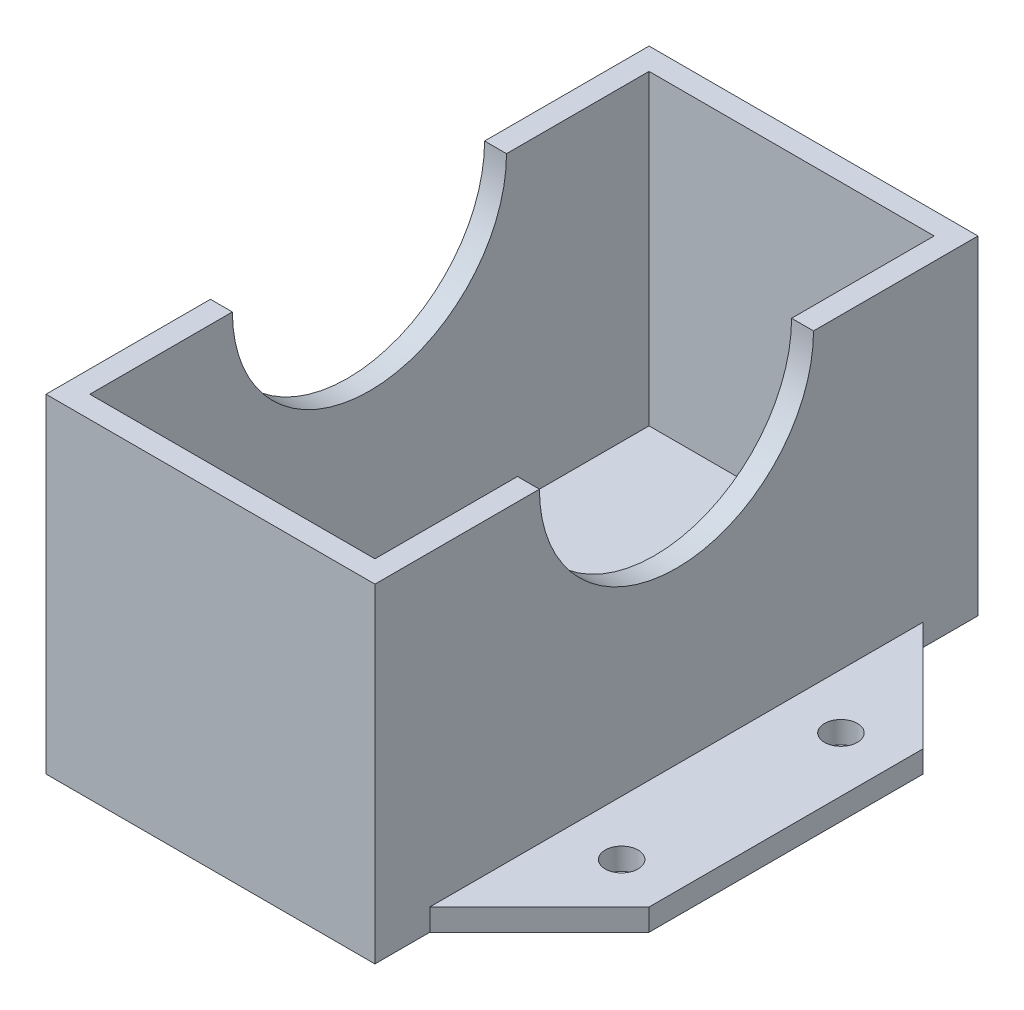
SolidWorks part; units mm, degrees
material "PLA 50%"
ref_plane "Front Plane" through (0, 0, 0) normal (0, 0, 1) x (1, 0, 0)
ref_plane "Top Plane" through (0, 0, 0) normal (0, 1, 0) x (1, 0, 0)
ref_plane "Right Plane" through (0, 0, 0) normal (1, 0, 0) x (0, 0, -1)
ref_axis "X" through (-88.99, 0, 0) along (1, 0, 0)
ref_axis "Y" through (0, 55, 0) along (0, -1, 0)
ref_axis "Z" through (0, 0, -88.99) along (0, 0, 1)
sketch "Sketch1" plane through (0, 0, 0) normal (0, 1, 0) x (1, 0, 0)
  line L0 (0, -27.5) -> (0, 27.5)
  line L5 (0, 27.5) -> (-15, 27.5)
  line L6 (-15, 27.5) -> (-15, 22.5)
  line L7 (-15, 22.5) -> (-25, 12.5)
  line L8 (-25, 12.5) -> (-25, -12.5)
  line L10 (-15, -22.5) -> (-15, -27.5)
  line L11 (-15, -27.5) -> (0, -27.5)
  line L12 (-15, -22.5) -> (-25, -12.5)
  line L17 (-20, -10) -> (-20, 10) construction
  line L18 (-15, 0) -> (-25, 0) construction
  circle A0 centre (-20, 10) radius 1.5
  circle A1 centre (-20, -10) radius 1.5
  point P3 (0, 0)
  point P17 (-20, 0)
  point P20 (-20, 0)
  dimension "D5" = 3
  dimension "D1" = 5
  dimension "D2" = 15
  dimension "D3" = 10
  dimension "D4" = 55
  dimension "D6" = 20
  dimension "D7" = 135
extrude "Boss-Extrude1" add sketch "Sketch1" along normal blind 2
mirror "Mirror1" about plane through (0, 0, 0) normal (1, 0, 0) of "Boss-Extrude1"
sketch "Sketch2" plane through (0, 2, 0) normal (0, 1, 0) x (1, 0, 0)
  line L0 (-13, 25.5) -> (-13, -25.5)
  line L1 (-15, 27.5) -> (15, 27.5)
  line L2 (-15, 27.5) -> (-15, -27.5)
  line L3 (-15, -27.5) -> (15, -27.5)
  line L4 (15, 27.5) -> (15, -27.5)
  line L5 (-13, -25.5) -> (13, -25.5)
  line L6 (13, 25.5) -> (13, -25.5)
  line L7 (-13, 25.5) -> (13, 25.5)
  dimension "D1" = 2
extrude "Boss-Extrude2" add sketch "Sketch2" along normal blind 28
sketch "Sketch3" plane through (15, 0, 0) normal (1, 0, 0) x (0, 0, -1)
  line L0 (-27.5, 30) -> (27.5, 30) construction
  circle A0 centre (0, 30) radius 12.5
  dimension "D1" = 25
extrude "Cut-Extrude1" cut sketch "Sketch3" against normal through all
